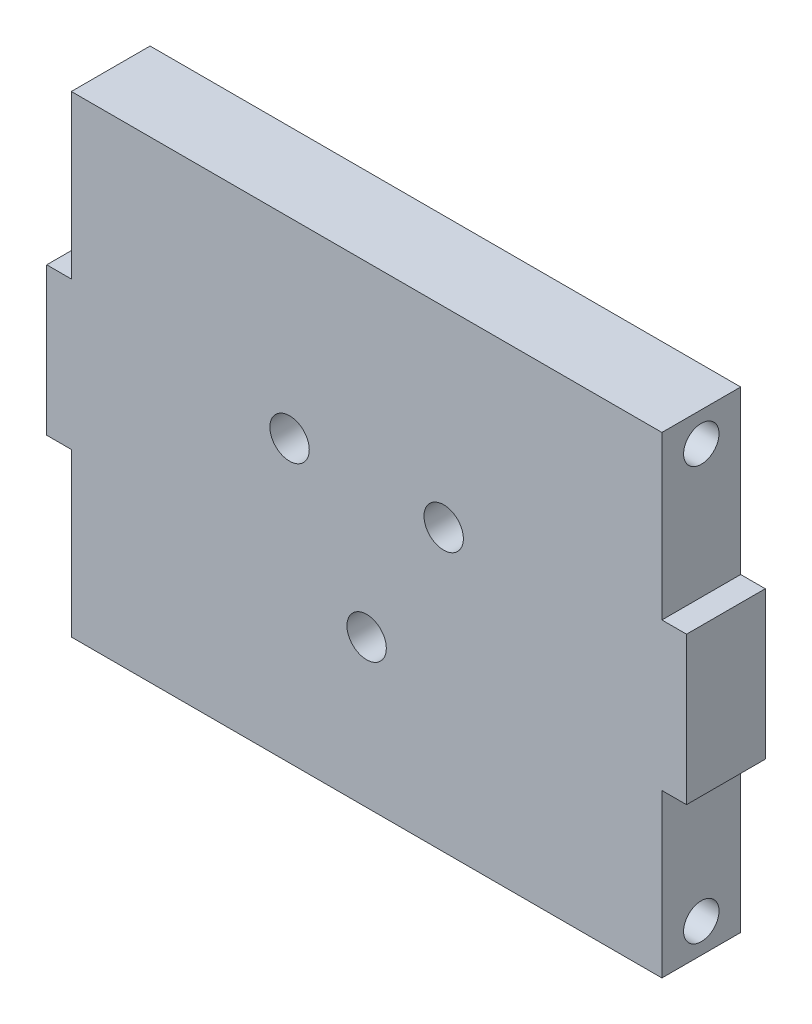
SolidWorks part; units mm, degrees
note: '?' marks a value the reader was unsure of.
material "3d打印 35%"
ref_plane "前视基准面" through (0, 0, 0) normal (0, 0, 1) x (1, 0, 0)
ref_plane "上视基准面" through (0, 0, 0) normal (0, 1, 0) x (1, 0, 0)
ref_plane "右视基准面" through (0, 0, 0) normal (1, 0, 0) x (0, 0, -1)
sketch "草图1" plane through (0, 0, 0) normal (0, 0, 1) x (1, 0, 0)
  line L1 (-30, 24) -> (30, 24)
  line L2 (-30, 24) -> (-30, -24)
  line L3 (-30, -24) -> (30, -24)
  line L4 (30, 24) -> (30, -24)
  line L5 (-30, 24) -> (30, -24) construction
  line L6 (-30, -24) -> (30, 24) construction
  point P0 (0, 0)
extrude "凸台-拉伸1" add sketch "草图1" along normal blind 8 contours L1 L4 L3 L2
sketch "草图2" plane through (0, 0, 8) normal (0, 0, 1) x (1, 0, 0)
  line L1 (-32.5, 7.5) -> (32.5, 7.5)
  line L2 (-32.5, 7.5) -> (-32.5, -7.5)
  line L3 (-32.5, -7.5) -> (32.5, -7.5)
  line L4 (32.5, 7.5) -> (32.5, -7.5)
  line L5 (-32.5, 7.5) -> (32.5, -7.5) construction
  line L6 (-32.5, -7.5) -> (32.5, 7.5) construction
  point P0 (0, 0)
extrude "凸台-拉伸2" add sketch "草图2" against normal blind 8
sketch "草图3" plane through (0, 0, 8) normal (0, 0, 1) x (1, 0, 0)
  circle A0 centre (0, -9) radius 2
  dimension "D1" = 9
extrude "切除-拉伸1" cut sketch "草图3" against normal blind 8
pattern_circular "阵列(圆周)1" count 3 every 120 about axis through (0, 0.0384, 0) along (0, 0, 1) of "切除-拉伸1"
ref_plane "基准面4" through (0, 0, 4) normal (0, 0, -1) x (-1, 0, 0)
ref_axis "基准轴1" through (30, 7.5, 4) along (0, 1, 0)?
sketch "草图4" plane through (30, 0, 0) normal (1, 0, 0) x (0, 0, -1)
  line L0 (-4, -26.4) -> (-4, 26.4) construction
  line L1 (-8, 24) -> (0, 24) construction
  circle A0 centre (-4, 21) radius 1.8
  dimension "D1" = 3
extrude "切除-拉伸2" cut sketch "草图4" against normal blind 3
ref_plane "基准面5" through (0, 0, 0) normal (0, 1, 0) x (1, 0, 0)
mirror "镜向1" about plane through (0, 0, 0) normal (0, 1, 0) of "切除-拉伸2"
ref_plane "基准面6" through (0, 0, 0) normal (1, 0, 0) x (0, 0, -1)
mirror "镜向2" about plane through (0, 0, 0) normal (1, 0, 0) of "镜向1", "切除-拉伸2"
